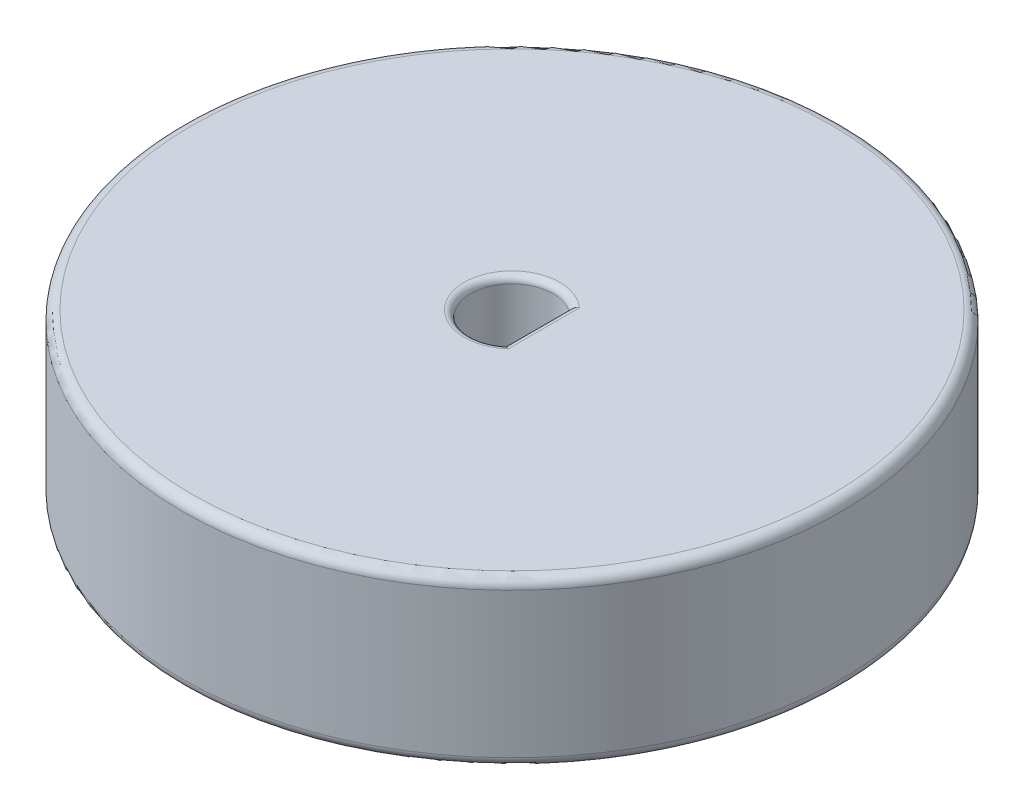
SolidWorks part; units mm, degrees
ref_plane "Front Plane" through (0, 0, 0) normal (0, 0, 1) x (1, 0, 0)
ref_plane "Top Plane" through (0, 0, 0) normal (0, 1, 0) x (1, 0, 0)
ref_plane "Right Plane" through (0, 0, 0) normal (1, 0, 0) x (0, 0, -1)
sketch "Sketch1" plane through (0, 0, 0) normal (0, 1, 0) x (1, 0, 0)
  line L0 (0.9779, 1.2505) -> (0.9779, -1.2505)
  circle A0 centre (0, 0) radius 12.7
  arc A2 (0.9779, 1.2505) -> (0.9779, -1.2505) centre (0, 0) ccw
  dimension "D1" = 25.4
  dimension "D2" = 0.9779
  dimension "D3" = 3.175
extrude "Boss-Extrude1" add sketch "Sketch1" along normal blind 6.35
fillet "Fillet1" radius 0.254 1 edges at (-1.5875, 6.35, 0)
fillet "Fillet2" radius 0.254 1 edges at (0.9779, 6.35, 0)
fillet "Fillet3" radius 0.254 2 edges at (0.9779, 0, 0) (-1.5875, 0, 0)
fillet "Fillet4" radius 0.381 2 edges at (0, 0, 12.7) (0, 6.35, 12.7)
